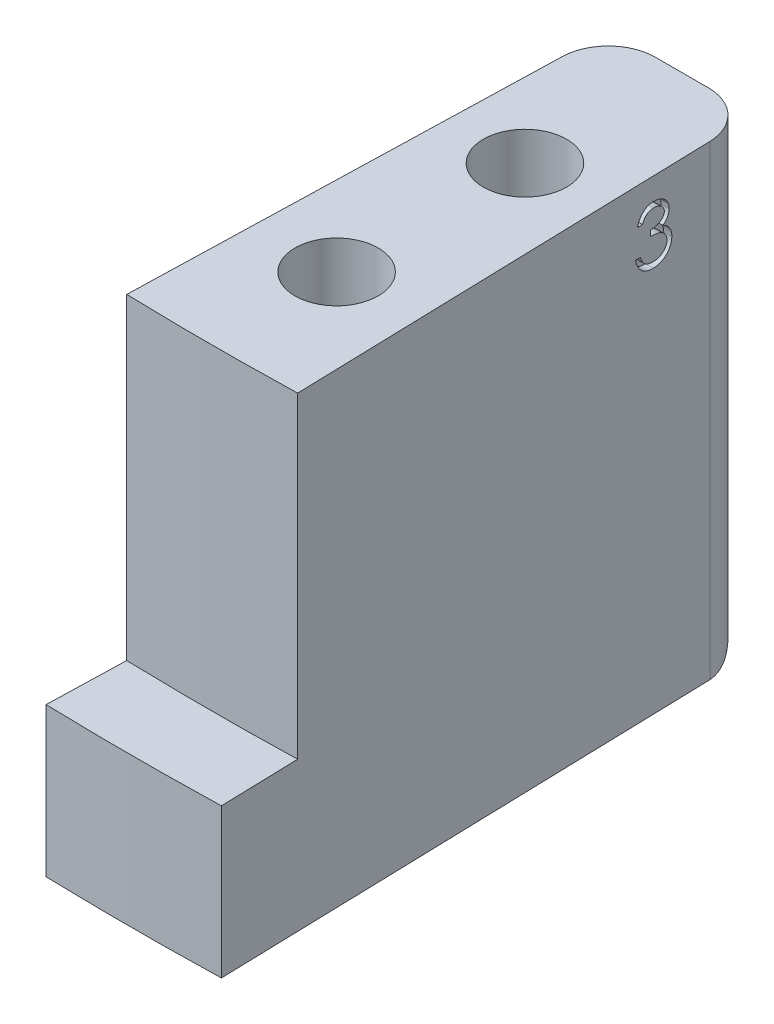
SolidWorks part; units mm, degrees
ref_plane "前视基准面" through (0, 0, 0) normal (0, 0, 1) x (1, 0, 0)
ref_plane "上视基准面" through (0, 0, 0) normal (0, 1, 0) x (1, 0, 0)
ref_plane "右视基准面" through (0, 0, 0) normal (1, 0, 0) x (0, 0, -1)
ref_axis "顶盖中心轴" through (0, -55, 0) along (0, 1, 0)
sketch "草图1" plane through (0, 0, 0) normal (0, 1, 0) x (1, 0, 0)
  line L0 (-4.7487, -170.0072) -> (-4.8586, -173.9402) construction
  line L1 (0, 0) -> (0, -125.794) construction
  line L3 (-4.6089, -165) -> (4.6089, -165)
  line L4 (-4.6089, -165) -> (-5.5843, -199.922)
  line L5 (4.6089, -165) -> (5.5843, -199.922)
  arc A0 (-5.4447, -194.924) -> (5.4447, -194.924) centre (0, 0) ccw
  arc A1 (-5.5843, -199.922) -> (5.5843, -199.922) centre (0, 0) ccw
  dimension "D1" = 1.6
  dimension "D2" = 195
  dimension "D4" = 200
  dimension "D3" = 165
extrude "主体" add sketch "草图1" along normal blind 29.7 contours L4 A0 L5 L3 region at (0, 0, 180.4033)
extrude "插销" add sketch "草图1<3>" along normal blind 9.5 contours L4 A1 L5 A0 region at (0, 0, 197.4849)
sketch "草图1<3>" plane through (0, 0, 0) normal (0, 1, 0) x (1, 0, 0) same geometry as "草图1"
ref_plane "对称面" through (0, 0, 0) normal (1, 0, 0) x (0, 0, -1)
fillet "圆角1" radius 3 3 edges at (-4.6089, 14.85, 165) (4.6089, 14.85, 165) (0, 0, 165)
hole_wizard "M5 间隙孔1" positions "草图4" profile "草图5" hole size "M5" standard "ISO" end condition up to next
sketch "草图4" plane through (0, 29.7, 0) normal (0, 1, 0) x (1, 0, 0)
  line L0 (0, -13.75) -> (0, 13.75) construction
  point P0 (0, -187)
  point P2 (0, -175)
  dimension "D1" = 175
  dimension "D2" = 187
sketch "草图5" plane through (0, 29.7, 187) normal (1, 0, 0) x (0, 0, 1)
  line L0 (0, 0) -> (0, 29.7)
  line L1 (0, 29.7) -> (2.65, 29.7)
  line L2 (2.65, 29.7) -> (2.65, 0)
  line L5 (2.65, 0) -> (0, 0)
  line L11 (0, -6.35) -> (0, 107.95) construction
  dimension "通孔孔直径" = 5.3
  dimension "通孔孔深度" = 29.7
sketch "草图6" plane through (0, 0, 0) normal (0, -1, 0) x (1, 0, 0)
  line L1 (0, 179.6188) -> (-4, 177.3094)
  line L2 (-4, 177.3094) -> (-4, 172.6906)
  line L3 (-4, 172.6906) -> (0, 170.3812)
  line L4 (0, 170.3812) -> (4, 172.6906)
  line L5 (4, 172.6906) -> (4, 177.3094)
  line L6 (4, 177.3094) -> (0, 179.6188)
  line L7 (0, 191.6188) -> (-4, 189.3094)
  line L8 (-4, 189.3094) -> (-4, 184.6906)
  line L9 (-4, 184.6906) -> (0, 182.3812)
  line L10 (0, 182.3812) -> (4, 184.6906)
  line L11 (4, 184.6906) -> (4, 189.3094)
  line L12 (4, 189.3094) -> (0, 191.6188)
  circle A0 centre (0, 175) radius 4 construction
  circle A1 centre (0, 187) radius 4 construction
  dimension "D1" = 8
  dimension "D2" = 8
extrude "切除-拉伸1" cut sketch "草图6" against normal blind 5
sketch "草图7" plane through (0, 0, 0) normal (0.9996, 0, -0.0279) x (-0.0279, 0, -0.9996)
  line L0 (-167.9817, 0.0012) -> (-167.9817, 29.7) construction
  line L2 (-167.9817, 29.7) -> (-195, 29.7) construction
  text T0 "3\r\n"
  dimension "D1" = 5
  dimension "D2" = 5
extrude "切除-拉伸2" cut sketch "草图7" against normal blind 0.5
